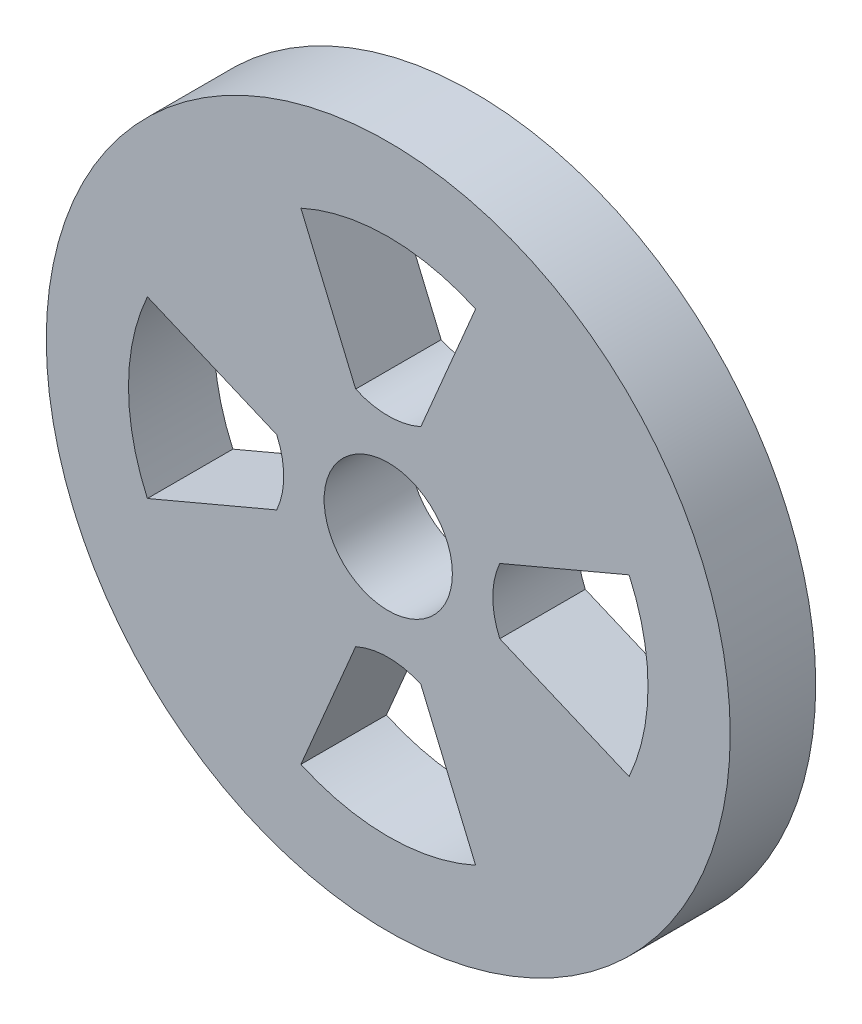
SolidWorks part; units mm, degrees
ref_plane "Piano frontale" through (0, 0, 0) normal (0, 0, 1) x (1, 0, 0)
ref_plane "Piano superiore" through (0, 0, 0) normal (0, 1, 0) x (1, 0, 0)
ref_plane "Piano destro" through (0, 0, 0) normal (1, 0, 0) x (0, 0, -1)
sketch "Schizzo1" plane through (0, 0, 0) normal (0, 0, 1) x (1, 0, 0)
  circle A0 centre (0, 0) radius 80
  circle A1 centre (0, 0) radius 15
extrude "Estrusione-Estrusione1" add sketch "Schizzo1" along normal mid plane 20
sketch "Schizzo2" plane through (0, 0, 10) normal (0, 0, 1) x (1, 0, 0)
  line L0 (-20.4333, 56.3439) -> (-7.6244, 26.0891)
  line L1 (20.4333, 56.3439) -> (7.6244, 26.0891)
  line L2 (56.3439, -20.4333) -> (26.0891, -7.6244)
  line L3 (56.3439, 20.4333) -> (26.0891, 7.6244)
  line L4 (-20.4333, -56.3439) -> (-7.6244, -26.0891)
  line L5 (20.4333, -56.3439) -> (7.6244, -26.0891)
  line L6 (-56.3439, 20.4333) -> (-26.0891, 7.6244)
  line L7 (-56.3439, -20.4333) -> (-26.0891, -7.6244)
  arc A0 (-20.4333, 56.3439) -> (20.4333, 56.3439) centre (0, 11.3557) cw
  arc A1 (-7.6244, 26.0891) -> (7.6244, 26.0891) centre (0, 42.9964) ccw
  arc A2 (26.0891, 7.6244) -> (26.0891, -7.6244) centre (42.9964, 0) ccw
  arc A3 (56.3439, 20.4333) -> (56.3439, -20.4333) centre (11.3557, 0) cw
  arc A4 (7.6244, -26.0891) -> (-7.6244, -26.0891) centre (0, -42.9964) ccw
  arc A5 (20.4333, -56.3439) -> (-20.4333, -56.3439) centre (0, -11.3557) cw
  arc A6 (-26.0891, -7.6244) -> (-26.0891, 7.6244) centre (-42.9964, 0) ccw
  arc A7 (-56.3439, -20.4333) -> (-56.3439, 20.4333) centre (-11.3557, 0) cw
  point P26 (0, 0)
  dimension "D2" = 4
extrude "Taglio-Estrusione1" cut sketch "Schizzo2" against normal through all
